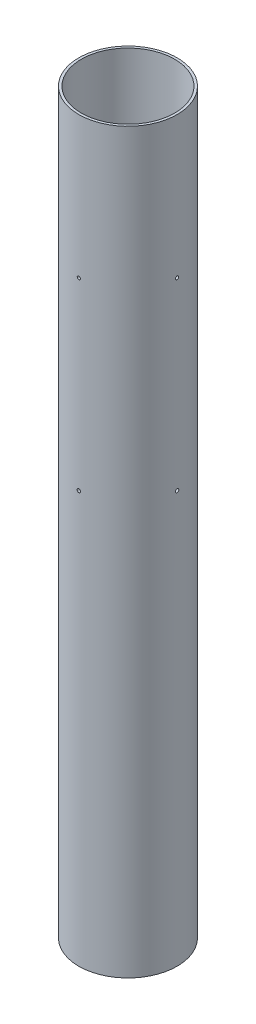
SolidWorks part; units mm, degrees
material "E-Glass Fiber"
ref_plane "Front Plane" through (0, 0, 0) normal (0, 0, 1) x (1, 0, 0)
ref_plane "Top Plane" through (0, 0, 0) normal (0, 1, 0) x (1, 0, 0)
ref_plane "Right Plane" through (0, 0, 0) normal (1, 0, 0) x (0, 0, -1)
sketch "Sketch1" plane through (0, 0, 0) normal (0, 1, 0) x (1, 0, 0)
  circle A0 centre (0, 0) radius 50.8
  dimension "D1" = 101.6
extrude "Coupler Extrusion" add sketch "Sketch1" along normal blind 762 thin thin type one direction reverse wall 2.54
ref_plane "Plane1" through (0, 0, 50.8) normal (0, 0, 1) x (1, 0, 0)
sketch "Sketch2" plane through (0, 0, 50.8) normal (0, 0, 1) x (1, 0, 0)
  line L0 (0, 762) -> (0, 0) construction
  line L1 (48.26, 762) -> (-48.26, 762) construction
  circle A0 centre (0, 615.95) radius 1.6383
  dimension "D1" = 3.2766
  dimension "D2" = 146.05
extrude "Bulkhead Hole" cut sketch "Sketch2" against normal up to next
pattern_circular "CirPattern1" count 4 over 360 about axis through (0, 762, 0) along (0, -1, 0) of "Bulkhead Hole"
sketch "Sketch3" plane through (0, 0, 50.8) normal (0, 0, 1) x (1, 0, 0)
  line L0 (0, 762) -> (0, 0) construction
  line L1 (50.8, 762) -> (-50.8, 762) construction
  line L2 (-48.26, 0) -> (48.26, 0) construction
  line L3 (-50.8, 0) -> (50.8, 0) construction
  line L4 (48.26, 762) -> (-48.26, 762) construction
  circle A0 centre (0, 425.45) radius 1.7526
  dimension "D1" = 3.5052
  dimension "D2" = 425.45
  dimension "D3" = 336.55
extrude "Lower Bulkhead Hole" cut sketch "Sketch3" against normal up to next
pattern_circular "CirPattern2" count 4 over 360 about axis through (0, 762, 0) along (0, -1, 0) of "Lower Bulkhead Hole" reverse direction yes
